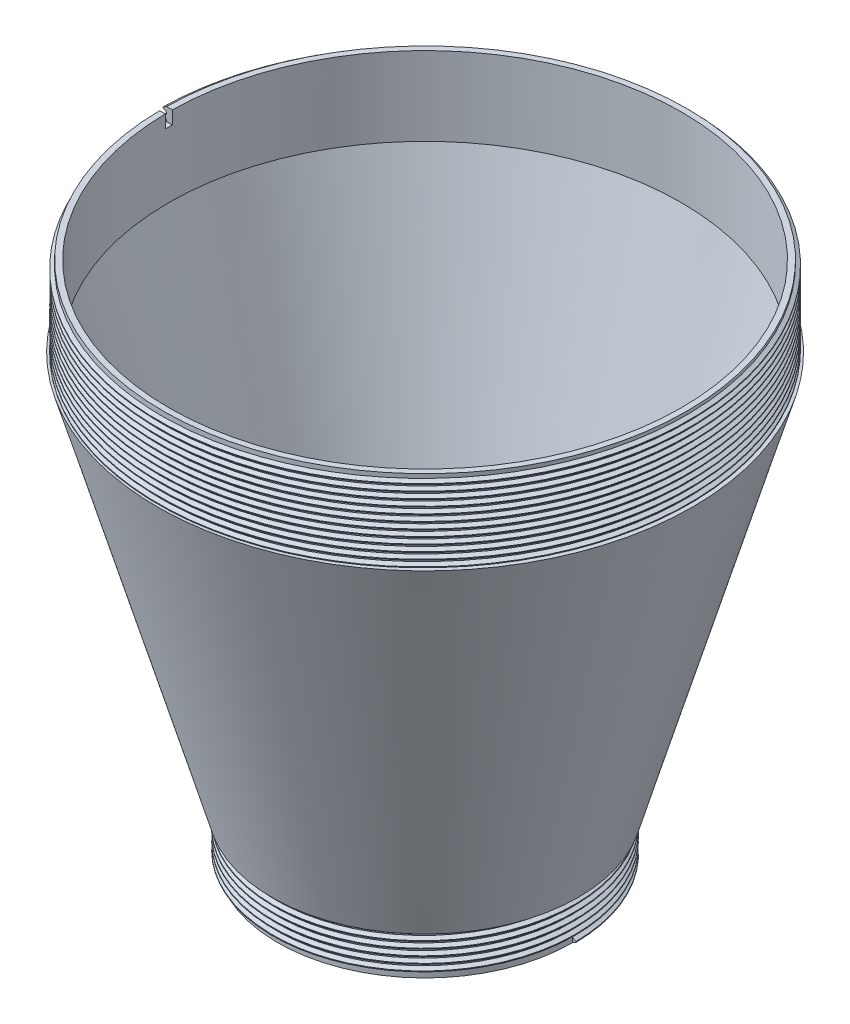
SolidWorks part; units mm, degrees
ref_plane "Front Plane" through (0, 0, 0) normal (0, 0, 1) x (1, 0, 0)
ref_plane "Top Plane" through (0, 0, 0) normal (0, 1, 0) x (1, 0, 0)
ref_plane "Right Plane" through (0, 0, 0) normal (1, 0, 0) x (0, 0, -1)
sketch "Sketch1" plane through (0, 0, 0) normal (0, 0, 1) x (1, 0, 0)
  line L0 (0, -1000) -> (0, 49000) construction
  line L12 (-35.1, -40.0417) -> (-61.3, 50.5173)
  line L26 (-35.1, -40.0417) -> (-68.3675, 74.9459) construction
  line L27 (-32.5, -39.6731) -> (-64.9087, 72.3459) construction
  line L29 (-32.5, -39.6731) -> (-58.7, 50.8859)
  line L31 (-32.5, -73.891) -> (-32.5, -39.6731) construction
  line L36 (-68.3675, 74.9459) -> (-35, 74.9459) construction
  line L37 (-64.9087, 72.3459) -> (-35, 72.3459) construction
  line L41 (-2.9583, -72.5541) -> (-32.5, -72.5541) construction
  line L42 (-0.0924, -75.1541) -> (-32.5, -75.1541) construction
  line L43 (-1.2805, -62.9707) -> (-0.0924, -75.1541) construction
  line L44 (-32.5, -73.891) -> (-1.2805, -62.9707) construction
  line L45 (-35.1, -77.555) -> (-35.1, -40.0417) construction
  line L46 (-35.1, -77.555) -> (-3.547, -66.5179) construction
  line L50 (-3.547, -66.5179) -> (-2.9583, -72.5541) construction
  line L53 (-32.5, -39.7088) -> (-32.5, -49.7088)
  line L54 (-32.5, -49.7088) -> (-33.75, -49.7088)
  line L55 (-33.75, -49.7088) -> (-33.75, -40.0343)
  line L56 (-33.75, -40.0343) -> (-35.1, -40.0343)
  line L57 (-35.1, -40.0343) -> (-35.1, -40.0417)
  line L58 (-32.5, -39.7088) -> (-32.5, -39.6731)
  line L59 (-58.7, 50.8859) -> (-58.7, 68.8859)
  line L60 (-61.3, 50.5173) -> (-60, 50.5173)
  line L62 (-60, 68.8859) -> (-58.7, 68.8859)
  line L63 (-60, 50.5173) -> (-60, 68.8859)
  dimension "D5" = 2.6
  dimension "D1" = 32.5
  dimension "D6" = 1.25
  dimension "D7" = 60
  dimension "D2" = 10
  dimension "D3" = 2.6
  dimension "D4" = 2.6
  dimension "D8" = 18
  dimension "D9" = 1.3
revolve "Revolve1" add sketch "Sketch1" angle 360 about L0
thread "Thread1" pitch 1.5 method extrude profile "Thread Profile1" start angle 0, offset 0, length 0, pitch 1.5, diameter 67.5
ref_plane "Plane1" through (33.75, -49.7088, 0) normal (0, 0, 1) x (1, 0, 0)
sketch "Thread Profile1" plane through (33.75, -49.7088, 0) normal (0, 0, 1) x (1, 0, 0)
  line L0 (0, 0) -> (0, 1.5) construction
  line L1 (0, 0) -> (0.8119, 0.4687)
  line L2 (0.8119, 0.4687) -> (0.8119, 0.6562)
  line L3 (0.8119, 0.6562) -> (0, 1.125)
  line L4 (0.8119, 0.5625) -> (0, 0.5625) construction
  line L11 (0, 0) -> (0, 1.125)
  point P2 (0, 0)
  dimension "Pitch" = 1.5
  dimension "Profile_Angle" = 60
  dimension "Profile_Land" = 0.1875
  dimension "Profile_Height" = 0.8119
thread "Thread2" pitch 1.5 method extrude profile "Thread Profile2" start angle 0, offset 0, length 0, pitch 1.5, diameter 120
ref_plane "Plane2" through (-60, 68.8859, 0) normal (0, 0, 1) x (-1, 0, 0)
sketch "Thread Profile2" plane through (-60, 68.8859, 0) normal (0, 0, 1) x (-1, 0, 0)
  line L0 (0, 0) -> (0, 1.5) construction
  line L1 (0, 0) -> (0.8119, 0.4687)
  line L2 (0.8119, 0.4687) -> (0.8119, 0.6562)
  line L3 (0.8119, 0.6562) -> (0, 1.125)
  line L4 (0.8119, 0.5625) -> (0, 0.5625) construction
  line L11 (0, 0) -> (0, 1.125)
  point P2 (0, 0)
  dimension "Pitch" = 1.5
  dimension "Profile_Angle" = 60
  dimension "Profile_Land" = 0.1875
  dimension "Profile_Height" = 0.8119
sketch "Sketch2" plane through (0, 0, 0) normal (1, 0, 0) x (0, 0, -1)
  line L0 (-0.8051, 68.8828) -> (-0.8051, 69.699)
  line L2 (0.8044, 68.8828) -> (0.8044, 65.8889)
  line L3 (0.8044, 65.8889) -> (-0.8051, 65.8889)
  line L4 (-0.8051, 68.8828) -> (-0.8051, 65.8889)
  line L5 (0.8044, 68.8828) -> (-0.8051, 65.8889) construction
  line L6 (0.8044, 65.8889) -> (-0.8051, 68.8828) construction
  line L7 (-0.8051, 69.699) -> (0.8044, 69.699)
  line L8 (0.8044, 69.699) -> (0.8044, 68.8828)
  spline S0 degree 2 poles (0, 68.8859) (24.8528, 68.7921) (42.4264, 68.6984) (60, 68.6046) (60, 68.5109) (60, 68.4171) (42.4264, 68.3234) (24.8528, 68.2296) (0, 68.1359) (-24.8528, 68.0421) (-42.4264, 67.9484) (-60, 67.8546) (-60, 67.7609) (-60, 67.6671) (-42.4264, 67.5734) (-24.8528, 67.4796) (0, 67.3859) (24.8528, 67.2921) (42.4264, 67.1984) (60, 67.1046) (60, 67.0109) (60, 66.9171) (42.4264, 66.8234) (24.8528, 66.7296) (0, 66.6359) (-24.8528, 66.5421) (-42.4264, 66.4484) (-60, 66.3546) (-60, 66.2609) (-60, 66.1671) (-42.4264, 66.0734) (-24.8528, 65.9796) (0, 65.8859) (24.8528, 65.7921) (42.4264, 65.6984) (60, 65.6046) (60, 65.5109) (60, 65.4171) (42.4264, 65.3234) (24.8528, 65.2296) (0, 65.1359) (-24.8528, 65.0421) (-42.4264, 64.9484) (-60, 64.8546) (-60, 64.7609) (-60, 64.6671) (-42.4264, 64.5734) (-24.8528, 64.4796) (0, 64.3859) (24.8528, 64.2921) (42.4264, 64.1984) (60, 64.1046) (60, 64.0109) (60, 63.9171) (42.4264, 63.8234) (24.8528, 63.7296) (0, 63.6359) (-24.8528, 63.5421) (-42.4264, 63.4484) (-60, 63.3546) (-60, 63.2609) (-60, 63.1671) (-42.4264, 63.0734) (-24.8528, 62.9796) (0, 62.8859) (24.8528, 62.7921) (42.4264, 62.6984) (60, 62.6046) (60, 62.5109) (60, 62.4171) (42.4264, 62.3234) (24.8528, 62.2296) (0, 62.1359) (-24.8528, 62.0421) (-42.4264, 61.9484) (-60, 61.8546) (-60, 61.7609) (-60, 61.6671) (-42.4264, 61.5734) (-24.8528, 61.4796) (0, 61.3859) (24.8528, 61.2921) (42.4264, 61.1984) (60, 61.1046) (60, 61.0109) (60, 60.9171) (42.4264, 60.8234) (24.8528, 60.7296) (0, 60.6359) (-24.8528, 60.5421) (-42.4264, 60.4484) (-60, 60.3546) (-60, 60.2609) (-60, 60.1671) (-42.4264, 60.0734) (-24.8528, 59.9796) (0, 59.8859) (24.8528, 59.7921) (42.4264, 59.6984) (60, 59.6046) (60, 59.5109) (60, 59.4171) (42.4264, 59.3234) (24.8528, 59.2296) (0, 59.1359) (-24.8528, 59.0421) (-42.4264, 58.9484) (-60, 58.8546) (-60, 58.7609) (-60, 58.6671) (-42.4264, 58.5734) (-24.8528, 58.4796) (0, 58.3859) (24.8528, 58.2921) (42.4264, 58.1984) (60, 58.1046) (60, 58.0109) (60, 57.9171) (42.4264, 57.8234) (24.8528, 57.7296) (0, 57.6359) (-24.8528, 57.5421) (-42.4264, 57.4484) (-60, 57.3546) (-60, 57.2609) (-60, 57.1671) (-42.4264, 57.0734) (-24.8528, 56.9796) (0, 56.8859) (24.8528, 56.7921) (42.4264, 56.6984) (60, 56.6046) (60, 56.5109) (60, 56.4171) (42.4264, 56.3234) (24.8528, 56.2296) (0, 56.1359) (-24.8528, 56.0421) (-42.4264, 55.9484) (-60, 55.8546) (-60, 55.7609) (-60, 55.6671) (-42.4264, 55.5734) (-24.8528, 55.4796) (0, 55.3859) (24.8528, 55.2921) (42.4264, 55.1984) (60, 55.1046) (60, 55.0109) (60, 54.9171) (42.4264, 54.8234) (24.8528, 54.7296) (0, 54.6359) (-24.8528, 54.5421) (-42.4264, 54.4484) (-60, 54.3546) (-60, 54.2609) (-60, 54.1671) (-42.4264, 54.0734) (-24.8528, 53.9796) (0, 53.8859) (24.8528, 53.7921) (42.4264, 53.6984) (60, 53.6046) (60, 53.5109) (60, 53.4171) (42.4264, 53.3234) (24.8528, 53.2296) (0, 53.1359) (-24.8528, 53.0421) (-42.4264, 52.9484) (-60, 52.8546) (-60, 52.7609) (-60, 52.6671) (-42.4264, 52.5734) (-24.8528, 52.4796) (0, 52.3859) (24.8528, 52.2921) (42.4264, 52.1984) (60, 52.1046) (60, 52.0109) (60, 51.9171) (42.4264, 51.8234) (24.8528, 51.7296) (0, 51.6359) (-24.8528, 51.5421) (-42.4264, 51.4484) (-60, 51.3546) (-60, 51.2609) (-60, 51.1671) (-42.4264, 51.0734) (-24.8528, 50.9796) (0, 50.8859) (24.8528, 50.7921) (42.4264, 50.6984) (59.3, 50.6084) (59.9759, 50.5173) knots 0 0 0 0.009615 0.009615 0.019231 0.019231 0.028846 0.028846 0.038462 0.038462 0.048077 0.048077 0.057692 0.057692 0.067308 0.067308 0.076923 0.076923 0.086538 0.086538 0.096154 0.096154 0.105769 0.105769 0.115385 0.115385 0.125 0.125 0.134615 0.134615 0.144231 0.144231 0.153846 0.153846 0.163462 0.163462 0.173077 0.173077 0.182692 0.182692 0.192308 0.192308 0.201923 0.201923 0.211538 0.211538 0.221154 0.221154 0.230769 0.230769 0.240385 0.240385 0.25 0.25 0.259615 0.259615 0.269231 0.269231 0.278846 0.278846 0.288462 0.288462 0.298077 0.298077 0.307692 0.307692 0.317308 0.317308 0.326923 0.326923 0.336538 0.336538 0.346154 0.346154 0.355769 0.355769 0.365385 0.365385 0.375 0.375 0.384615 0.384615 0.394231 0.394231 0.403846 0.403846 0.413462 0.413462 0.423077 0.423077 0.432692 0.432692 0.442308 0.442308 0.451923 0.451923 0.461538 0.461538 0.471154 0.471154 0.480769 0.480769 0.490385 0.490385 0.5 0.5 0.509615 0.509615 0.519231 0.519231 0.528846 0.528846 0.538462 0.538462 0.548077 0.548077 0.557692 0.557692 0.567308 0.567308 0.576923 0.576923 0.586538 0.586538 0.596154 0.596154 0.605769 0.605769 0.615385 0.615385 0.625 0.625 0.634615 0.634615 0.644231 0.644231 0.653846 0.653846 0.663462 0.663462 0.673077 0.673077 0.682692 0.682692 0.692308 0.692308 0.701923 0.701923 0.711538 0.711538 0.721154 0.721154 0.730769 0.730769 0.740385 0.740385 0.75 0.75 0.759615 0.759615 0.769231 0.769231 0.778846 0.778846 0.788462 0.788462 0.798077 0.798077 0.807692 0.807692 0.817308 0.817308 0.826923 0.826923 0.836538 0.836538 0.846154 0.846154 0.855769 0.855769 0.865385 0.865385 0.875 0.875 0.884615 0.884615 0.894231 0.894231 0.903846 0.903846 0.913462 0.913462 0.923077 0.923077 0.932692 0.932692 0.941953 0.941953 0.941953 weights 1 0.92388 1 0.92388 1 0.92388 1 0.92388 1 0.92388 1 0.92388 1 0.92388 1 0.92388 1 0.92388 1 0.92388 1 0.92388 1 0.92388 1 0.92388 1 0.92388 1 0.92388 1 0.92388 1 0.92388 1 0.92388 1 0.92388 1 0.92388 1 0.92388 1 0.92388 1 0.92388 1 0.92388 1 0.92388 1 0.92388 1 0.92388 1 0.92388 1 0.92388 1 0.92388 1 0.92388 1 0.92388 1 0.92388 1 0.92388 1 0.92388 1 0.92388 1 0.92388 1 0.92388 1 0.92388 1 0.92388 1 0.92388 1 0.92388 1 0.92388 1 0.92388 1 0.92388 1 0.92388 1 0.92388 1 0.92388 1 0.92388 1 0.92388 1 0.92388 1 0.92388 1 0.92388 1 0.92388 1 0.92388 1 0.92388 1 0.92388 1 0.92388 1 0.92388 1 0.92388 1 0.92388 1 0.92388 1 0.92388 1 0.92388 1 0.92388 1 0.92388 1 0.92388 1 0.92388 1 0.92388 1 0.92388 1 0.92388 1 0.92388 1 0.92388 1 0.92388 1 0.92388 1 0.92388 1 0.92388 1 0.92388 1 0.92388 1 0.92388 1 0.92388 1 0.92388 1 0.92388 1 0.92388 1 0.92388 1 0.92388 1 0.92388 1 0.92388 1 0.92388 1 0.92388 1 0.92388 1 0.92388 1 0.92388 1 0.92388 1 0.92388 1 0.92388 1 0.92388 1 0.926689 0.994588 construction
  point P0 (-0.0003, 67.3859)
extrude "Cut-Extrude1" cut sketch "Sketch2" against normal blind 100
